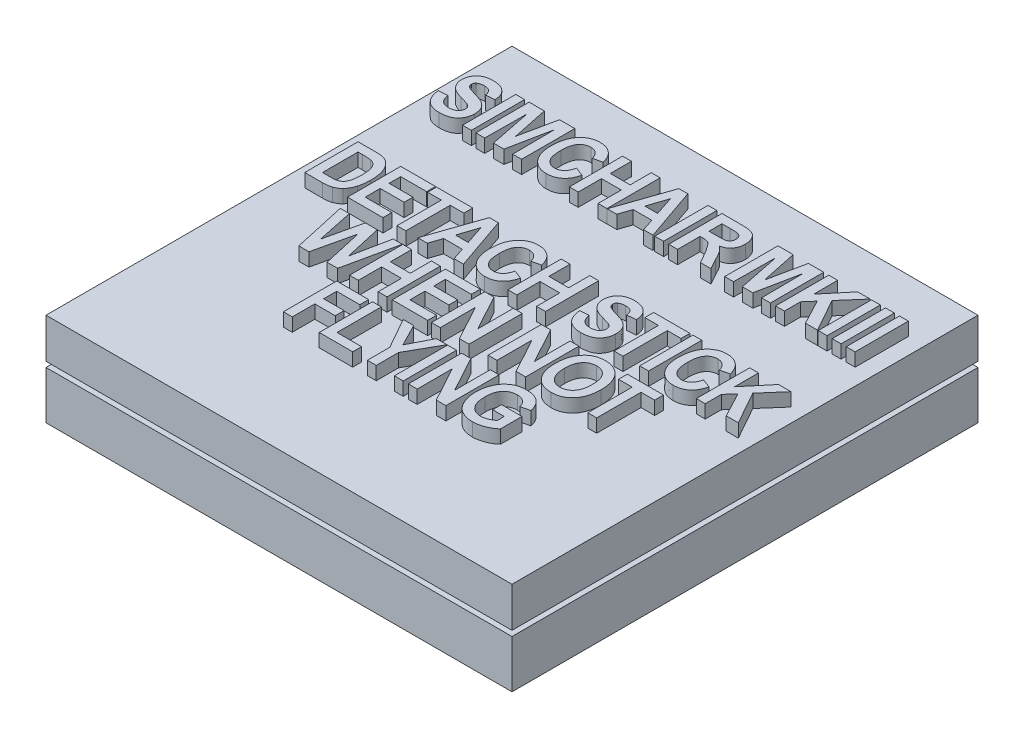
SolidWorks part; units mm, degrees
ref_plane "Спереди" through (0, 0, 0) normal (0, 0, 1) x (1, 0, 0)
ref_plane "Сверху" through (0, 0, 0) normal (0, 1, 0) x (1, 0, 0)
ref_plane "Справа" through (0, 0, 0) normal (1, 0, 0) x (0, 0, -1)
sketch "Sketch1" plane through (0, 0, 0) normal (0, 1, 0) x (1, 0, 0)
  line L1 (14.85, -14.85) -> (-14.85, -14.85)
  line L2 (14.85, -14.85) -> (14.85, 14.85)
  line L3 (14.85, 14.85) -> (-14.85, 14.85)
  line L4 (-14.85, -14.85) -> (-14.85, 14.85)
  line L5 (14.85, -14.85) -> (-14.85, 14.85) construction
  line L6 (14.85, 14.85) -> (-14.85, -14.85) construction
  point P0 (0, 0)
  dimension "D1" = 29.7
  dimension "D2" = 29.7
extrude "Boss-Extrude1" add sketch "Sketch1" along normal blind 4
sketch "Sketch2" plane through (0, 4, 0) normal (0, 1, 0) x (1, 0, 0)
  line L1 (17.5, -17.5) -> (-17.5, -17.5)
  line L2 (17.5, -17.5) -> (17.5, 17.5)
  line L3 (17.5, 17.5) -> (-17.5, 17.5)
  line L4 (-17.5, -17.5) -> (-17.5, 17.5)
  line L5 (17.5, -17.5) -> (-17.5, 17.5) construction
  line L6 (17.5, 17.5) -> (-17.5, -17.5) construction
  point P0 (0, 0)
  dimension "D1" = 35
extrude "Boss-Extrude2" add sketch "Sketch2" along normal blind 3
sketch "Sketch3" plane through (0, 7, 0) normal (0, 1, 0) x (1, 0, 0)
  line L0 (-17.5, 9.5) -> (17.5, 9.5) construction
  line L1 (-17.5, 17.5) -> (-17.5, -17.5) construction
  line L2 (17.5, -17.5) -> (17.5, 17.5) construction
  line L3 (17.5, 17.5) -> (-17.5, 17.5) construction
  text T0 "<b>SIMCHAIR MKIII</b>" font "Arial" height 4
  dimension "D1" = 8
extrude "Boss-Extrude3" add sketch "Sketch3" along normal blind 1
sketch "Sketch7" plane through (0, 7, 0) normal (0, 1, 0) x (1, 0, 0)
  line L0 (-17.5, 0.5) -> (17.5, 0.5) construction
  line L1 (-17.5, 17.5) -> (-17.5, -17.5) construction
  line L2 (17.5, -17.5) -> (17.5, 17.5) construction
  line L3 (17.5, 17.5) -> (-17.5, 17.5) construction
  text T0 "<b>DETACH STICK</b>" font "Arial" height 4
  dimension "D1" = 17
extrude "Boss-Extrude4" add sketch "Sketch7" along normal blind 1
sketch "Sketch8" plane through (0, 7, 0) normal (0, 1, 0) x (1, 0, 0)
  line L0 (-17.5, -4.5) -> (17.5, -4.5) construction
  line L1 (-17.5, 17.5) -> (-17.5, -17.5) construction
  line L2 (17.5, -17.5) -> (17.5, 17.5) construction
  line L3 (17.5, 17.5) -> (-17.5, 17.5) construction
  text T0 "<b>WHEN NOT</b>" font "Arial" height 4
  dimension "D1" = 22
extrude "Boss-Extrude5" add sketch "Sketch8" along normal blind 1
sketch "Sketch9" plane through (0, 7, 0) normal (0, 1, 0) x (1, 0, 0)
  line L0 (-17.5, -9.3635) -> (17.5, -9.3635) construction
  line L1 (-17.5, 17.5) -> (-17.5, -17.5) construction
  line L2 (17.5, -17.5) -> (17.5, 17.5) construction
  text T0 "<b>FLYING</b>" font "Arial" height 4
extrude "Boss-Extrude6" add sketch "Sketch9" along normal blind 1
chamfer "Chamfer1" distance 1 angle 60 4 edges at (14.85, 0, 0) (0, 0, 14.85) (-14.85, 0, 0) (0, 0, -14.85) first distance on face at (0, 0, 0)
sketch "Sketch10" plane through (0, 0, 0) normal (0, -1, 0) x (1, 0, 0)
  line L0 (17.5, 17.5) -> (17.5, -17.5) construction
  line L1 (-15.25, 15.25) -> (15.25, 15.25)
  line L2 (-15.25, 15.25) -> (-15.25, -15.25)
  line L3 (-15.25, -15.25) -> (15.25, -15.25)
  line L4 (15.25, 15.25) -> (15.25, -15.25)
  line L5 (-15.25, 15.25) -> (15.25, -15.25) construction
  line L6 (-15.25, -15.25) -> (15.25, 15.25) construction
  line L7 (-17.5, 17.5) -> (17.5, 17.5)
  line L8 (-17.5, 17.5) -> (-17.5, -17.5)
  line L9 (-17.5, -17.5) -> (17.5, -17.5)
  line L10 (17.5, 17.5) -> (17.5, -17.5)
  line L11 (-17.5, 17.5) -> (17.5, -17.5) construction
  line L12 (-17.5, -17.5) -> (17.5, 17.5) construction
  line L13 (14.85, 14.85) -> (14.85, -14.85) construction
  point P0 (0, 0)
  point P6 (0, 0)
  dimension "D1" = 0.4
extrude "Boss-Extrude7" add sketch "Sketch10" against normal offset from surface (3.6 mm away) 0.4 separate body up to face at (0, 4, 0)
